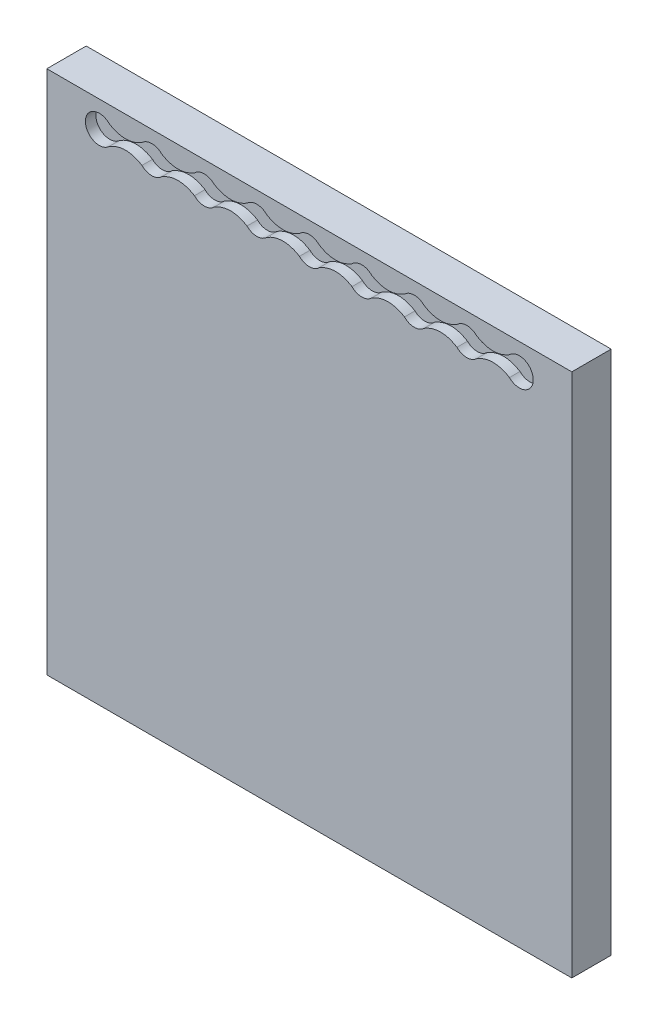
SolidWorks part; units mm, degrees
ref_plane "Front Plane" through (0, 0, 0) normal (0, 0, 1) x (1, 0, 0)
ref_plane "Top Plane" through (0, 0, 0) normal (0, 1, 0) x (1, 0, 0)
ref_plane "Right Plane" through (0, 0, 0) normal (1, 0, 0) x (0, 0, -1)
sketch "Sketch2" plane through (0, 0, 0) normal (0, 0, 1) x (1, 0, 0)
  line L1 (-31.0609, 95.629) -> (95.9391, 95.629)
  line L2 (-31.0609, 95.629) -> (-31.0609, -31.371)
  line L3 (-31.0609, -31.371) -> (95.9391, -31.371)
  line L4 (95.9391, 95.629) -> (95.9391, -31.371)
  dimension "D1" = 127
  dimension "D2" = 127
extrude "Boss-Extrude1" add sketch "Sketch2" along normal blind 9.525
sketch "Sketch1" plane through (0, 0, 9.525) normal (0, 0, 1) x (1, 0, 0)
  line L0 (-23.8319, 89.279) -> (-5.6609, 89.279) construction
  line L1 (-18.3609, 89.279) -> (-18.3609, 88.3231) construction
  line L2 (-12.0109, 79.8143) -> (-12.0109, 100.2941) construction
  line L3 (-18.3609, 89.279) -> (-12.0109, 95.629) construction
  line L4 (-12.0109, 95.629) -> (-5.6609, 89.279) construction
  line L5 (-19.5823, 90.4697) -> (-15.4837, 90.4697) construction
  line L6 (95.9391, 95.629) -> (-31.0609, 95.629) construction
  line L9 (-31.0609, 95.629) -> (-31.0609, -31.371) construction
  arc A0 (-15.9755, 91.6644) -> (-15.9755, 86.8937) centre (-18.3609, 89.279) ccw
  arc A1 (-8.0463, 86.8937) -> (-8.0463, 91.6644) centre (-5.6609, 89.279) ccw
  spline S0 degree 2 poles (-15.9755, 91.6644) (-12.0109, 89.2749) (-8.0463, 91.6644) knots 0 0 0 1 1 1
  spline S1 degree 2 poles (-15.9755, 86.8937) (-12.0109, 89.2832) (-8.0463, 86.8937) knots 0 0 0 1 1 1
  point P6 (-15.9755, 91.6644)
  point P10 (-8.0463, 91.6644)
  point P20 (0, 0)
  point P22 (0, 0)
  point P24 (0, 0)
  point P25 (-5.873, 89.279)
  dimension "D1" = 6.7469
  dimension "D2" = 6.7469
  dimension "D3" = 12.7
  dimension "D4" = 1.1906
  dimension "D5" = 6.35
  dimension "D6" = 12.7
extrude "Cut-Extrude1" cut sketch "Sketch1" against normal blind 2.54
pattern_linear "LPattern1" count 8 spacing 12.7 along (1, 0, 0) of "Cut-Extrude1"
equation "\"large_diameter\" = 1/4in"
equation "\"small_diameter\" = 1/8in"
equation "\"arc_height\" = 1/32in"
equation "\"chain_space\" = 1/2in"
equation "\"chain_thickness\" = 1/32in"
equation "\"outer_height\" = 3/16in"
equation "\"inner_height\" = 2/16in"
equation "\"give\" = 1/64in"
equation "\"board_base\" = 10"
equation "\"board_rows\" = 3"
equation "\"D2@Sketch1\"= \"large_diameter\" + \"give\""
equation "\"D3@Sketch1\"= \"chain_space\""
equation "\"D4@Sketch1\"= \"arc_height\" + \"give\""
equation "\"D1@Sketch2\"=\"chain_space\"*(\"board_base\")"
equation "\"D3@LPattern1\"=\"chain_space\""
equation "\"D1@LPattern1\"=\"board_base\"-2"
